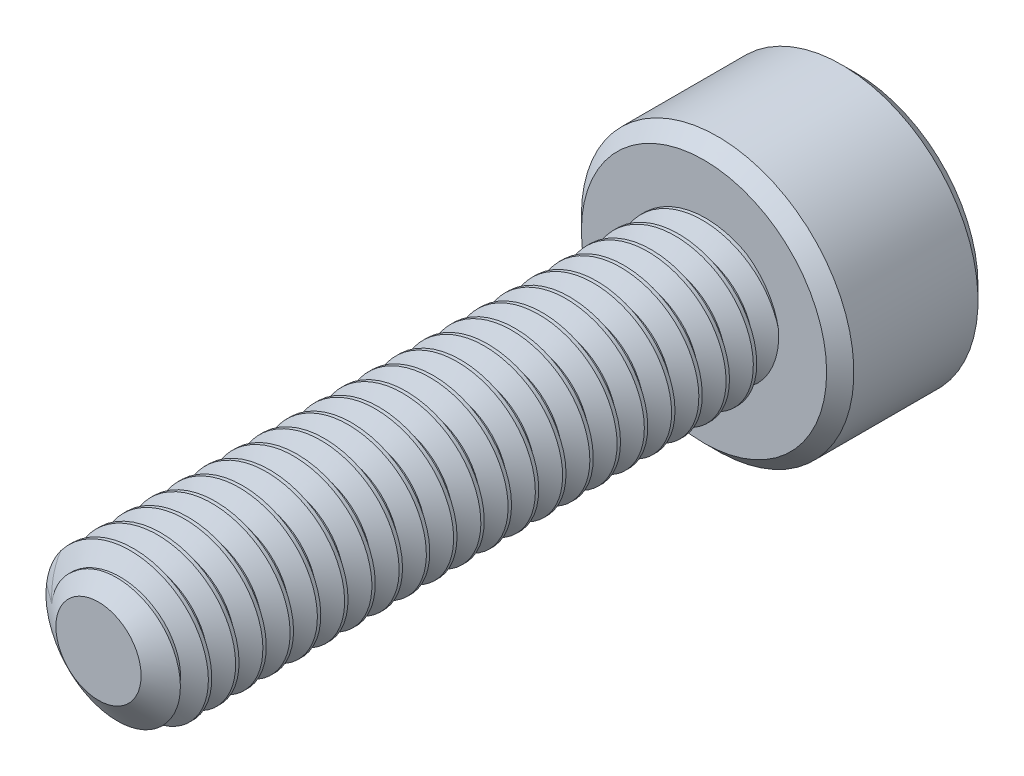
SolidWorks part; units mm, degrees
other "DetailItem1"
ref_plane "Front Plane" through (0, 0, 0) normal (0, 0, 1) x (1, 0, 0)
ref_plane "Top Plane" through (0, 0, 0) normal (0, 1, 0) x (1, 0, 0)
ref_plane "Right Plane" through (0, 0, 0) normal (1, 0, 0) x (0, 0, -1)
sketch "Sketch1" plane through (0, 0, 0) normal (0, 0, 1) x (1, 0, 0)
  circle A0 centre (0, 0) radius 1.25
  dimension "OD" = 2.5
extrude "Extrude1" add sketch "Sketch1" against normal blind 10
sketch "Sketch2" plane through (0, 0, 0) normal (0, 0, 1) x (1, 0, 0)
  circle A0 centre (0, 0) radius 1.25 construction
  circle A1 centre (0, 0) radius 1.25
curve "Helix/Spiral1" pitch 0.45 height 10.45 radius 1.25 centre (0, 0, 0) axis (0, 0, -1) start towards (0, 1, 0) parameters "pitch"=0.45
sketch "Sketch3" plane through (0, 0, 0) normal (1, 0, 0) x (0, 0, -1)
  line L0 (-0.3937, 1.25) -> (-0.225, 0.9577)
  line L1 (-0.225, 0.9577) -> (-0.1688, 0.9577)
  line L2 (-0.1688, 0.9577) -> (0, 1.25)
  line L3 (-0.3937, 1.25) -> (0, 1.25)
  line L4 (-0.1969, 1.25) -> (-0.1969, 0.9577) construction
  line L5 (-0.3094, 1.1039) -> (-0.0844, 1.1039) construction
  line L6 (0, 1.25) -> (0, -1.25) construction
  dimension "D1" = 0.0563
  dimension "D2" = 0.225
  dimension "D3" = 60
sweep "Cut-Sweep1" cut profiles "Sketch3" path "Helix/Spiral1"
sketch "Sketch4" plane through (0, 0, 0) normal (1, 0, 0) x (0, 0, -1)
  line L0 (0.3825, 1.25) -> (0, 0.7037)
  line L1 (0, 0.7037) -> (0, 1.25)
  line L2 (0.3825, 1.25) -> (0, 1.25)
  line L3 (-0.3937, 1.25) -> (0, 1.25) construction
  line L4 (0, 0) -> (7.0209, 0) construction
  dimension "D1" = 55
  dimension "D2" = 0.254
revolve "Cut-Revolve1" cut sketch "Sketch4" angle 360 about L4
sketch "Sketch6" plane through (0, 0, -10) normal (0, 0, -1) x (-1, 0, 0)
  circle A0 centre (0, 0) radius 2.25
  dimension "head dia" = 4.5
extrude "Extrude2" add sketch "Sketch6" along normal blind 2.5
sketch "Sketch7" plane through (0, 0, -12.5) normal (0, 0, -1) x (-1, 0, 0)
  line L1 (0, 1.1547) -> (-1, 0.5774)
  line L2 (-1, 0.5774) -> (-1, -0.5774)
  line L3 (-1, -0.5774) -> (0, -1.1547)
  line L4 (0, -1.1547) -> (1, -0.5774)
  line L5 (1, -0.5774) -> (1, 0.5774)
  line L6 (1, 0.5774) -> (0, 1.1547)
  circle A0 centre (0, 0) radius 1 construction
  dimension "hex dia" = 2
extrude "Cut-Extrude1" cut sketch "Sketch7" against normal blind 1.5
sketch "Sketch8" plane through (0, 0, -12.5) normal (0, 0, -1) x (-1, 0, 0)
  circle A0 centre (0, 0) radius 1.1547
extrude "Cut-Extrude2" cut sketch "Sketch8" against normal through all draft 45
chamfer "Chamfer1" distance 0.225 angle 45 2 edges at (-2.25, 0, -12.5) (-2.25, 0, -10)
sketch "Sketch10" plane through (0, 0, -10) normal (0, 0, 1) x (1, 0, 0)
  circle A1 centre (0, 0) radius 1.25
  circle A2 centre (0, 0) radius 1.25
  dimension "D1" = 0
ref_plane "Plane1" through (0, 0, 0) normal (0, 0, 1) x (1, 0, 0)
extrude "partial thread" [suppressed] add sketch "Sketch10" along normal up to surface (8 mm away) separate body up to plane "Plane1"
chamfer "Chamfer2" [suppressed] distance 0.05 angle 45
combine bodies "Combine1" [suppressed] operation type add bodies to combine 107 108
sketch "Sketch9" plane through (0, 0, 0) normal (1, 0, 0) x (0, 0, -1)
  line L0 (0, 1.25) -> (0, -1.25) construction
  line L1 (1.125, 1.25) -> (1.125, -1.25) construction
  dimension "D1" = 1.125
equation "\"D3@Helix/Spiral1\" = \"screw length@Extrude1\"+\"pitch@Helix/Spiral1\""
equation "\"D1@Sketch3\" = \"pitch@Helix/Spiral1\"*.125"
equation "\"D2@Sketch3\" = \"pitch@Helix/Spiral1\"*.5"
equation "\"D1@Cut-Extrude1\" = \"hex dia@Sketch7\"*.75"
equation "\"D1@Chamfer1\" = \"head dia@Sketch6\"*.05"
equation "\"D1@Sketch9\" = \"pitch@Helix/Spiral1\"*2.5"
equation "\"D1@Chamfer2\"=\"OD@Sketch1\"*.02"
